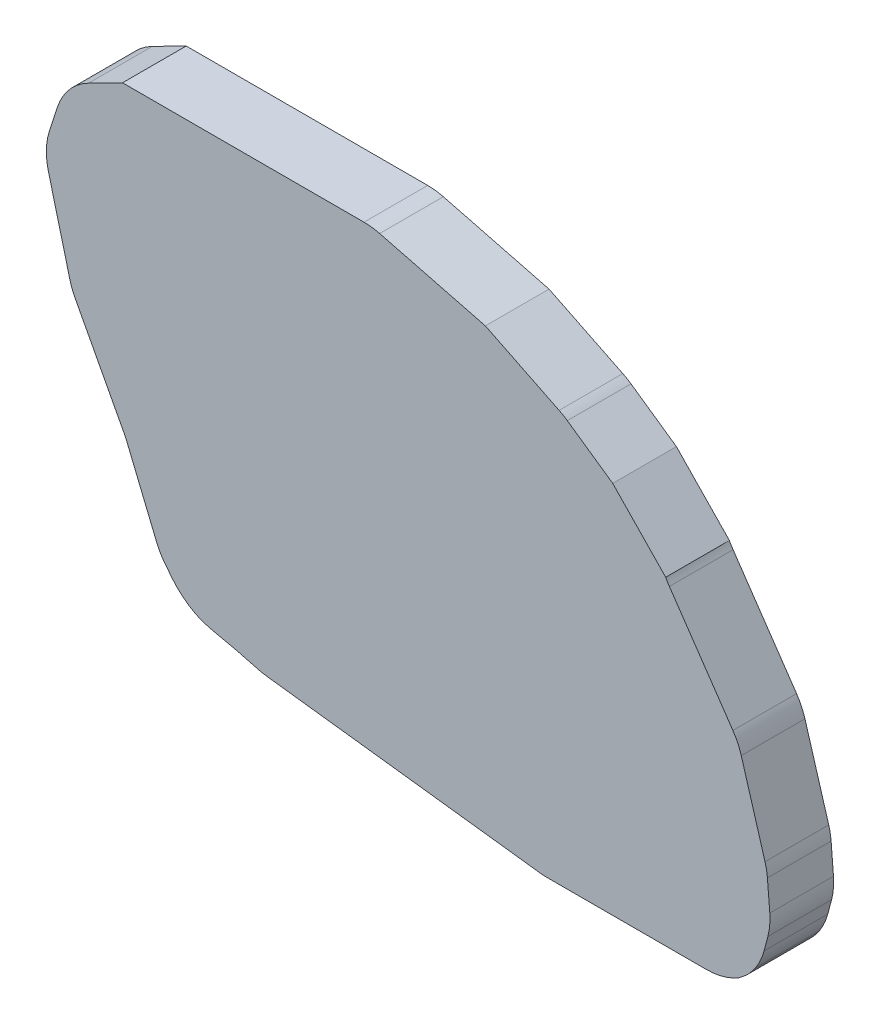
SolidWorks part; units mm, degrees
ref_plane "Front Plane" through (0, 0, 0) normal (0, 0, 1) x (1, 0, 0)
ref_plane "Top Plane" through (0, 0, 0) normal (0, 1, 0) x (1, 0, 0)
ref_plane "Right Plane" through (0, 0, 0) normal (1, 0, 0) x (0, 0, -1)
sketch "Sketch1" plane through (0, 0, 0) normal (0, 0, 1) x (1, 0, 0)
  line L0 (96, 288) -> (480, 288) construction
  line L5 (139.8875, 204.0569) -> (141.2478, 208.2423)
  line L6 (141.2478, 208.2423) -> (144.8357, 210.0701)
  line L7 (144.8357, 210.0701) -> (160.5008, 210.0701)
  line L8 (160.5008, 210.0701) -> (167.6223, 208.2423)
  line L9 (167.6223, 208.2423) -> (172.5227, 205.8317)
  line L10 (172.5227, 205.8317) -> (175.6197, 203.6755)
  line L11 (175.6197, 203.6755) -> (178.9468, 200.2338)
  line L12 (178.9468, 200.2338) -> (179.0371, 200.0565)
  line L13 (179.0371, 200.0565) -> (183.516, 193.5019)
  line L14 (183.516, 193.5019) -> (185.3016, 187.4874)
  line L15 (185.3016, 187.4874) -> (185.5391, 184.5636)
  line L16 (185.5391, 184.5636) -> (184.9544, 182.3551)
  line L17 (184.9544, 182.3551) -> (184.1138, 181.11)
  line L18 (184.1138, 181.11) -> (182.6519, 180.178)
  line L19 (182.6519, 180.178) -> (181.2323, 180.178)
  line L20 (181.2323, 180.178) -> (171.2716, 180.178)
  line L21 (171.2716, 180.178) -> (153.6307, 182.3551)
  line L22 (153.6307, 182.3551) -> (151.9661, 182.7893)
  line L23 (151.9661, 182.7893) -> (149.3848, 183.3631)
  line L24 (149.3848, 183.3631) -> (148.2087, 184.3681)
  line L25 (148.2087, 184.3681) -> (147.1895, 185.6438)
  line L26 (147.1895, 185.6438) -> (145.0293, 190.8839)
  line L27 (145.0293, 190.8839) -> (141.6449, 197.2747)
  line L28 (141.6449, 197.2747) -> (139.8875, 204.0569)
  point P24 (184.4487, 181.8762)
  point P27 (185.4939, 181.1082)
  point P28 (184.2567, 180.0203)
  point P29 (185.2273, 181.2042)
  point P30 (183.8345, 179.999)
  point P31 (0, 0)
  point P32 (183.1702, 193.1314)
  point P33 (0, 0)
  point P34 (154.7887, 183.0064)
  point P35 (149.4572, 185.1052)
  point P36 (146.0798, 185.1052)
  point P37 (149.1677, 183.0064)
  point P38 (151.9661, 182.7893)
  point P39 (153.6307, 182.3551)
  point P40 (149.3848, 183.3631)
  point P41 (147.1895, 184.4056)
  point P42 (145.0293, 190.8839)
  point P43 (147.1895, 185.6438)
  point P44 (148.2087, 184.3681)
  point P45 (183.1702, 180.1376)
  point P46 (185.0034, 181.4629)
  point P47 (183.701, 192.269)
  point P48 (183.516, 193.5019)
  point P49 (183.516, 192.531)
  point P50 (184.5795, 187.4758)
  point P51 (185.3747, 183.3631)
  point P52 (184.2965, 181.9505)
  point P53 (184.5795, 181.512)
  point P54 (185.3564, 183.9241)
  point P55 (185.3366, 187.6153)
  point P56 (185.2102, 182.5353)
  point P57 (184.4244, 181.3292)
  point P58 (0, 0)
  point P59 (185.667, 184.3681)
  point P60 (184.9544, 182.3551)
  point P61 (184.1138, 181.11)
  point P62 (182.6519, 180.178)
  point P63 (185.5391, 184.5636)
  point P64 (185.3016, 187.4874)
  point P65 (178.9468, 200.2338)
  point P66 (172.5227, 205.8317)
  point P67 (0, 0)
  point P68 (175.6197, 203.6755)
  point P69 (167.6223, 208.2423)
extrude "Boss-Extrude1" add sketch "Sketch1" along normal blind 4
scale "Scale4" scale about centroid uniform scaling yes scale factor 0.75919
fillet "Fillet6" radius 3 15 edges at (170.0892, 203.1921, 2) (179.7908, 189.2653, 2) (175.0349, 198.8077, 2) (179.5272, 185.3689, 2) (178.4353, 193.8315, 2) (178.8891, 184.4237, 2) (169.1394, 183.7161, 2) (154.4829, 185.6986, 2) (155.7466, 185.3689, 2) (150.8565, 187.8657, 2) (151.6303, 186.8972, 2) (152.5232, 186.1343, 2) (177.7792, 183.7161, 2) (146.6471, 196.6958, 2) (149.2165, 191.8439, 2)
fillet "Fillet7" radius 3 4 edges at (145.3129, 201.8447, 2) (146.3456, 205.0223, 2) (160.9623, 206.4099, 2) (179.9712, 187.0457, 2)
